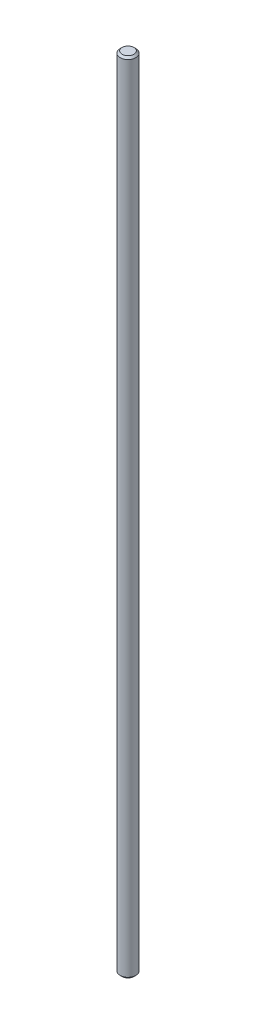
SolidWorks part; units mm, degrees
material "Plain Carbon Steel"
ref_plane "Front Plane" through (0, 0, 0) normal (0, 0, 1) x (1, 0, 0)
ref_plane "Top Plane" through (0, 0, 0) normal (0, 1, 0) x (1, 0, 0)
ref_plane "Right Plane" through (0, 0, 0) normal (1, 0, 0) x (0, 0, -1)
sketch "Sketch1" plane through (0, 0, 0) normal (0, 1, 0) x (1, 0, 0)
  circle A0 centre (0, 0) radius 4
  dimension "D1" = 8
extrude "Boss-Extrude1" add sketch "Sketch1" along normal blind 405
chamfer "Chamfer1" distance 1 angle 45 2 edges at (0, 405, 4) (0, 0, 4)
